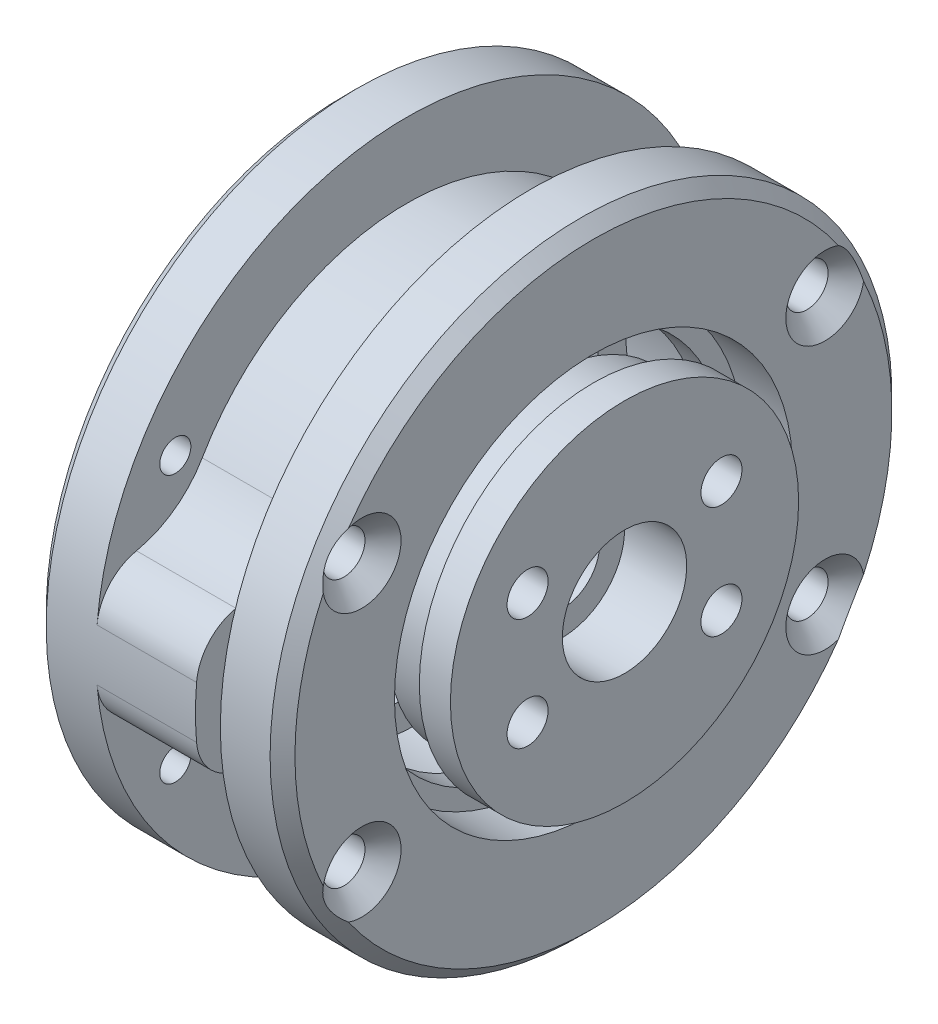
SolidWorks part; units mm, degrees
other "2808HM-innerBase"
other "2808HM-innerCap"
other "2808HM-outerBase"
other "2808HM-outerCap" parameters "D1"=33.3422, "D2"=15.696, "D3"=8, "D4"=9.8032, "D5"=2.0994, "D6"=4.1475, "D7"=3.4547, "32"=16, "D8"=3.4547, "D9"=6, "D10"=6, "D11"=2.5, "D12"=1.4276, "D13"=28, "D14"=10, "D15"=4.4283, "D16"=0.5299, "D17"=0.5299, "D18"=0.5299, "D19"=1.2328, "D20"=4, "D21"=8, "D22"=5, "D23"=2
ref_plane "Front Plane" through (0, 0, 0) normal (0, 0, 1) x (1, 0, 0)
ref_plane "Top Plane" through (0, 0, 0) normal (0, 1, 0) x (1, 0, 0)
ref_plane "Right Plane" through (0, 0, 0) normal (1, 0, 0) x (0, 0, -1)
sketch "Sketch1" plane through (0, 0, 0) normal (0, 0, 1) x (1, 0, 0)
  line L0 (0, 0) -> (0, 14) construction
  line L1 (-4, 14) -> (4, 14) construction
  line L2 (-4, 14) -> (-4, 9.5) construction
  line L3 (-4, 9.5) -> (4, 9.5) construction
  line L4 (4, 14) -> (4, 9.5) construction
  line L5 (0, 14) -> (0, 14.7) construction
  line L6 (-4, 16.7) -> (4, 16.7) construction
  line L7 (-4, 16.7) -> (-4, 14.7) construction
  line L8 (-4, 14.7) -> (4, 14.7) construction
  line L9 (4, 16.7) -> (4, 14.7) construction
  line L10 (-18.538, 0) -> (18.178, 0) construction
  line L11 (-10, 16) -> (-6, 16) construction
  line L12 (-10, 16) -> (-6, 16) construction
  line L13 (-10, 16) -> (-10, 12.5) construction
  line L14 (-10, 12.5) -> (-6, 12.5) construction
  line L15 (-6, 16) -> (-6, 12.5) construction
  line L16 (-6, 16) -> (-6, 14.5) construction
  line L17 (-10, 16) -> (-10, 25) construction
  line L18 (-4, 14.5) -> (-4, 16.7) construction
  line L19 (-4, 16.7) -> (4, 16.7) construction
  line L20 (-5, 19) -> (3, 19) construction
  line L21 (-6, 14.5) -> (-4, 14.5) construction
  line L22 (-4, 6.5) -> (4, 6.5) construction
  line L23 (-4, 7.5) -> (-6, 9.5) construction
  line L24 (-6, 9.5) -> (-6, 12.5) construction
  line L25 (-6, 12.5) -> (-10, 12.5) construction
  line L26 (-10, 12.5) -> (-10, 14) construction
  line L27 (-10, 14) -> (-12.5, 14) construction
  line L28 (-12.5, 14) -> (-12.5, 0) construction
  line L31 (-4, 7.5) -> (-4, 6.5) construction
  line L33 (4, 6.5) -> (4, 0) construction
  line L34 (4, 16.7) -> (4, 14.5) construction
  line L35 (4, 14.5) -> (6, 14.5) construction
  line L36 (6, 14.5) -> (6, 16) construction
  line L37 (6, 16) -> (10, 16) construction
  line L38 (10, 16) -> (10, 25) construction
  line L41 (4, 7.5) -> (6, 9.5) construction
  line L42 (6, 9.5) -> (6, 12.5) construction
  line L43 (6, 12.5) -> (10, 12.5) construction
  line L44 (10, 12.5) -> (10, 14) construction
  line L45 (10, 14) -> (12.5, 14) construction
  line L46 (12.5, 14) -> (12.5, 0) construction
  line L47 (4, 7.5) -> (4, 6.5) construction
  line L48 (10, 25) -> (5, 25) construction
  line L49 (5, 25) -> (5, 19) construction
  line L50 (5, 19) -> (3, 19) construction
  line L51 (-5, 19) -> (-5, 25) construction
  line L52 (-5, 25) -> (-10, 25) construction
  line L53 (3, 19) -> (3, 16.7) construction
  dimension "D4" = 8
  dimension "D5" = 2
  dimension "D8" = 4
  dimension "D9" = 2
  dimension "D10" = 10
  dimension "D7" = 12.5
  dimension "D11" = 1.5
  dimension "D12" = 1.5
  dimension "D13" = 28
  dimension "D3" = 33.4
  dimension "D2" = 8
  dimension "D15" = 6.5
  dimension "D18" = 1
  dimension "D17" = 8
  dimension "D20" = 32
  dimension "D6" = 25
  dimension "D14" = 10
  dimension "D22" = 50
  dimension "D23" = 1
  dimension "D21" = 38
  dimension "D16" = 45
sketch "Sketch2" plane through (0, 0, 0) normal (0, 0, 1) x (1, 0, 0)
  line L0 (-4, 6.5) -> (4, 6.5) construction
  line L1 (-4, 6.5) -> (5, 6.5)
  line L2 (-4, 7.5) -> (-4, 6.5) construction
  line L3 (-4, 7.5) -> (-4, 6.5)
  line L6 (-4, 7.5) -> (-6, 9.5) construction
  line L7 (-4, 7.5) -> (-6, 9.5)
  line L8 (-6, 9.5) -> (-6, 12.5) construction
  line L9 (-6, 9.5) -> (-6, 12.5)
  line L10 (-10, 12.5) -> (-6, 12.5) construction
  line L11 (-10, 12.5) -> (-6, 12.5)
  line L12 (-10, 16) -> (-10, 12.5) construction
  line L13 (-10, 14) -> (-10, 12.5)
  line L14 (-12.5, 14) -> (-12.5, 0) construction
  line L15 (-10, 14) -> (-12.5, 14) construction
  line L16 (-12.5, 14) -> (-12.5, 1.65)
  line L17 (-10, 14) -> (-12.5, 14)
  line L20 (-2.5, 3) -> (5, 3)
  line L21 (-2.5, 3) -> (-2.5, 1.65)
  line L22 (-2.5, 1.65) -> (-12.5, 1.65)
  line L23 (-18.538, 0) -> (18.178, 0) construction
  line L24 (-18.538, 0) -> (18.178, 0) construction
  line L25 (7.5, 5) -> (7.5, 0) construction
  line L26 (12.5, 14) -> (12.5, 0) construction
  line L27 (-12.5, 0) -> (-12.5, 1.65) construction
  line L28 (5, 6.5) -> (5, 3)
  line L29 (4, 7.5) -> (4, 6.5) construction
  dimension "D1" = 6
  dimension "D2" = 3.3
  dimension "D3" = 5
  dimension "D4" = 10
  dimension "D5" = 10
  dimension "10" = 10
  dimension "D6" = 1
revolve "Revolve1" add sketch "Sketch2" angle 360 about L24
sketch "Sketch3" plane through (0, 0, 0) normal (0, 0, 1) x (1, 0, 0)
  line L5 (5, -6.5) -> (5, 6.5) construction
  line L6 (5, 2.75) -> (3, 2.75)
  line L7 (5, 2.75) -> (5, 6.5)
  line L8 (5, 6.5) -> (3, 6.5)
  line L9 (3, 2.75) -> (3, 6.5)
  line L10 (-4, 6.5) -> (4, 6.5) construction
  line L11 (-18.538, 0) -> (18.178, 0) construction
  line L12 (-18.538, 0) -> (18.178, 0) construction
  line L13 (3, -2.75) -> (3, -6.5)
  line L14 (5, -6.5) -> (3, -6.5)
  line L15 (5, -2.75) -> (5, -6.5)
  line L16 (5, -2.75) -> (3, -2.75)
  dimension "D1" = 2
  dimension "D2" = 5.5
extrude "Cut-Extrude1" cut sketch "Sketch3" against normal through all both and the other way through all
sketch "Sketch4" plane through (0, 0, 0) normal (0, 0, 1) x (1, 0, 0)
  line L1 (4, 6.5) -> (6, 8.5)
  line L3 (6, 8.5) -> (6, 12.5)
  line L4 (6, 12.5) -> (10, 12.5) construction
  line L5 (6, 12.5) -> (10, 12.5)
  line L6 (10, 12.5) -> (10, 14) construction
  line L7 (10, 12.5) -> (10, 14)
  line L8 (10, 14) -> (12.5, 14) construction
  line L9 (10, 14) -> (12.5, 14)
  line L10 (12.5, 14) -> (12.5, 0) construction
  line L11 (12.5, 14) -> (12.5, 5)
  line L18 (3, 3) -> (7.5, 3)
  line L19 (7.5, 3) -> (7.5, 5)
  line L20 (7.5, 5) -> (12.5, 5)
  line L22 (3, 3) -> (3, 6.5)
  line L23 (-2.5, 3) -> (5, 3) construction
  line L24 (-18.538, 0) -> (18.178, 0) construction
  line L25 (-18.538, 0) -> (18.178, 0) construction
  line L27 (4, 6.5) -> (3, 6.5)
  line L28 (-4, 6.5) -> (4, 6.5) construction
  line L29 (3, 2.75) -> (3, 6.5) construction
  dimension "D1" = 45
revolve "Revolve2" add sketch "Sketch4" angle 360 about L25
sketch "Sketch5" plane through (0, 0, 0) normal (0, 0, 1) x (1, 0, 0)
  line L10 (-18.538, 0) -> (18.178, 0) construction
  line L11 (3, 2.75) -> (5, 2.75)
  line L12 (3, 2.75) -> (3, -2.75)
  line L13 (3, -2.75) -> (5, -2.75)
  line L14 (5, 2.75) -> (5, -2.75)
  line L15 (-18.538, 0) -> (18.178, 0) construction
  line L16 (5, -2.75) -> (5, 2.75) construction
extrude "Cut-Extrude8" cut sketch "Sketch5" against normal through all both and the other way through all
sketch "Sketch6" plane through (0, 0, 0) normal (0, 0, 1) x (1, 0, 0)
  line L6 (-10, 16) -> (-10, 25) construction
  line L7 (-10, 16) -> (-10, 25)
  line L8 (-10, 16) -> (-6, 16) construction
  line L9 (-10, 16) -> (-6, 16)
  line L10 (-6, 16) -> (-6, 12.5) construction
  line L11 (-6, 16) -> (-6, 14.5)
  line L12 (-6, 14.5) -> (-4, 14.5) construction
  line L13 (-6, 14.5) -> (-4, 14.5)
  line L14 (-4, 16.7) -> (-4, 14.7) construction
  line L15 (-4, 16.7) -> (-4, 14.5)
  line L16 (-18.538, 0) -> (18.178, 0) construction
  line L17 (-18.538, 0) -> (18.178, 0) construction
  line L18 (-5, 19) -> (-5, 25) construction
  line L19 (-5, 19) -> (-5, 25)
  line L20 (-5, 25) -> (-10, 25) construction
  line L21 (-5, 25) -> (-10, 25)
  line L22 (-5, 19) -> (3, 19) construction
  line L23 (-5, 19) -> (3, 19)
  line L24 (3, 19) -> (3, 16.7) construction
  line L25 (3, 19) -> (3, 16.7)
  line L26 (-4, 16.7) -> (4, 16.7) construction
  line L27 (-4, 16.7) -> (3, 16.7)
revolve "Revolve3" add sketch "Sketch6" angle 360 about L17
sketch "Sketch7" plane through (0, 0, 0) normal (0, 0, 1) x (1, 0, 0)
  line L0 (4, 16.7) -> (4, 14.5) construction
  line L1 (4, 16.7) -> (4, 14.5)
  line L4 (4, 14.5) -> (6, 14.5) construction
  line L5 (4, 14.5) -> (6, 14.5)
  line L6 (6, 14.5) -> (6, 16) construction
  line L7 (6, 14.5) -> (6, 16)
  line L8 (6, 16) -> (10, 16) construction
  line L9 (6, 16) -> (10, 16)
  line L12 (10, 16) -> (10, 25) construction
  line L13 (10, 16) -> (10, 25)
  line L14 (-18.538, 0) -> (18.178, 0) construction
  line L15 (-18.538, 0) -> (18.178, 0) construction
  line L16 (5, 19) -> (3, 19) construction
  line L17 (5, 19) -> (3, 19)
  line L18 (5, 25) -> (5, 19) construction
  line L19 (5, 25) -> (5, 19)
  line L20 (10, 25) -> (5, 25) construction
  line L21 (10, 25) -> (5, 25)
  line L22 (-4, 16.7) -> (4, 16.7) construction
  line L23 (3, 16.7) -> (4, 16.7)
  line L24 (3, 19) -> (3, 16.7) construction
  line L25 (3, 19) -> (3, 16.7)
revolve "Revolve4" add sketch "Sketch7" angle 360 about L15
sketch "Sketch8" plane through (-12.5, 0, 0) normal (-1, 0, 0) x (0, 0, 1)
  point P0 (0, 9)
  point P7 (7.7942, 4.5)
  point P8 (7.7942, -4.5)
  point P9 (0, -9)
  point P10 (0, 0)
  point P13 (-7.7942, -4.5)
  point P14 (-7.7942, 4.5)
  dimension "D1" = 9
  dimension "D2" = 6
hole_wizard "M4x0.7 Tapped Hole1" positions "Sketch8" profile "Sketch9" tap size "M4x0.7" standard "ANSI Metric"
sketch "Sketch9" plane through (-12.5, 4.5, -7.7942) normal (0, 1, 0) x (0, 0, 1)
  line L0 (0, 0) -> (0, 25)
  line L1 (0, 25) -> (1.65, 25)
  line L2 (1.65, 25) -> (1.65, 0)
  line L5 (1.65, 0) -> (0, 0)
  line L11 (0, -6.35) -> (0, 107.95) construction
  dimension "Thru Tap Drill Dia." = 3.3
  dimension "Thru Tap Drill Depth" = 25
cosmetic thread "Hole Thread2" parameters "D2"=4
cosmetic thread "Hole Thread3" parameters "D2"=4
cosmetic thread "Hole Thread9" parameters "D2"=4
cosmetic thread "Hole Thread10" parameters "D2"=4
sketch "Sketch10" plane through (0, 0, 0) normal (-1, 0, 0) x (0, 0, 1)
  line L0 (0, 0) -> (0, 27) construction
  line L1 (0, 0) -> (27, 0) construction
  line L2 (0, 0) -> (18.6195, 10.75) construction
  arc A9 (-16.4545, 9.5) -> (-16.4545, -9.5) centre (0, 0) ccw
  circle A29 centre (18.6195, 10.75) radius 1.65 construction
  circle A30 centre (18.6195, -10.75) radius 1.65 construction
  circle A31 centre (0, 0) radius 27 construction
  circle A32 centre (0, 0) radius 19 construction
  arc A33 (16.4545, -9.5) -> (16.4545, 9.5) centre (0, 0) ccw
  arc A34 (16.4545, 9.5) -> (21.7453, 5.6694) centre (23.3827, 13.5) ccw
  arc A35 (21.7453, 5.6694) -> (24.9126, 2.0881) centre (20.9266, 1.754) cw
  circle A36 centre (-18.6195, -10.75) radius 1.65 construction
  circle A38 centre (0, 0) radius 25 construction
  circle A42 centre (-18.6195, 10.75) radius 1.65 construction
  arc A43 (24.9126, 2.0881) -> (24.9126, -2.0881) centre (0, 0) cw
  arc A44 (16.4545, -9.5) -> (21.7453, -5.6694) centre (23.3827, -13.5) cw
  arc A45 (21.7453, -5.6694) -> (24.9126, -2.0881) centre (20.9266, -1.754) ccw
  arc A46 (-21.7453, 5.6694) -> (-24.9126, 2.0881) centre (-20.9266, 1.754) ccw
  arc A47 (-24.9126, 2.0881) -> (-24.9126, -2.0881) centre (0, 0) ccw
  arc A48 (-16.4545, 9.5) -> (-21.7453, 5.6694) centre (-23.3827, 13.5) cw
  arc A49 (-16.4545, -9.5) -> (-21.7453, -5.6694) centre (-23.3827, -13.5) ccw
  arc A50 (-21.7453, -5.6694) -> (-24.9126, -2.0881) centre (-20.9266, -1.754) cw
  dimension "D2" = 3.3
  dimension "D3" = 21.5
  dimension "D4" = 30
  dimension "D5" = 4
  dimension "D6" = 8
  dimension "D1" = 54
extrude "Boss-Extrude1" add sketch "Sketch10" along normal up to surface (5 mm away) and the other way blind 3 up to face at (-5, 0, 25)
sketch "Sketch14" plane through (10, 0, 0) normal (1, 0, 0) x (0, 0, -1)
  point P12 (-18.6195, -10.75)
  point P14 (-18.6195, 10.75)
  point P16 (18.6195, -10.75)
  point P18 (18.6195, 10.75)
hole_wizard "CSK for M3 Flat Head Machine Screw1" positions "Sketch14" profile "Sketch15" countersink size "M3" standard "ANSI Metric" end condition through all
sketch "Sketch15" plane through (10, -10.75, 18.6195) normal (0, 1, 0) x (0, 0, -1)
  line L0 (0, 0) -> (0, 22.5)
  line L1 (0, 22.5) -> (1.7, 22.5)
  line L2 (1.7, 22.5) -> (1.7, 1.45)
  line L3 (1.7, 1.45) -> (3.15, 0)
  line L5 (3.15, 0) -> (0, 0)
  line L6 (-1.7, 1.45) -> (-3.15, 0) construction
  line L11 (0, -6.35) -> (0, 107.95) construction
  dimension "Thru Hole Dia." = 3.4
  dimension "Thru Hole Depth" = 22.5
  dimension "Near C'Sink Dia." = 6.3
  dimension "Near C'Sink Angle" = 90
sketch "Sketch16" plane through (-10, 0, 0) normal (-1, 0, 0) x (0, 0, 1)
  point P12 (18.6195, 10.75)
  point P14 (18.6195, -10.75)
  point P16 (-18.6195, -10.75)
  point P18 (-18.6195, 10.75)
hole_wizard "M3x0.5 Tapped Hole1" positions "Sketch16" profile "Sketch17" tap size "M3x0.5" standard "ANSI Metric" end condition through all
sketch "Sketch17" plane through (-10, 10.75, 18.6195) normal (0, 1, 0) x (0, 0, 1)
  line L0 (0, 0) -> (0, 22.5)
  line L1 (0, 22.5) -> (1.25, 22.5)
  line L2 (1.25, 22.5) -> (1.25, 0)
  line L5 (1.25, 0) -> (0, 0)
  line L11 (0, -6.35) -> (0, 107.95) construction
  dimension "Thru Tap Drill Dia." = 2.5
  dimension "Thru Tap Drill Depth" = 22.5
cosmetic thread "Hole Thread5" parameters "D2"=3
cosmetic thread "Hole Thread6" parameters "D2"=3
cosmetic thread "Hole Thread7" parameters "D2"=3
cosmetic thread "Hole Thread8" parameters "D2"=3
chamfer "Chamfer2" distance 1 angle 45 1 edges at (10, 0, 25)
chamfer "Chamfer3" distance 1 angle 45 1 edges at (-10, 0, 25)
sketch "Sketch18" plane through (-12.5, 0, 0) normal (-1, 0, 0) x (0, 0, 1)
  line L0 (0, 0) -> (0, 18.4484) construction
  line L2 (-4.5, 13.2571) -> (-4.5, 7.2571)
  line L3 (-4.5, 7.2571) -> (4.5, 7.2571)
  line L4 (4.5, 7.2571) -> (4.5, 13.2571)
  circle A0 centre (0, 0) radius 14 construction
  arc A1 (-4.5, 13.2571) -> (4.5, 13.2571) centre (0, 0) cw
  dimension "D2" = 9
  dimension "D3" = 6
extrude "Cut-Extrude9" cut sketch "Sketch18" against normal through all
other "Save Bodies1"
equation "\"StatorDia\"= 28mm"
equation "\"StatorH\"= 8mm"
equation "\"CanDia\"= 33.4mm"
equation "\"D13@Sketch1\"=\"StatorDia\""
equation "\"D3@Sketch1\"=\"CanDia\""
equation "\"D2@Sketch1\"=\"StatorH\""
equation "\"CanH\"= 8mm"
equation "\"D4@Sketch1\"=\"CanH\""
